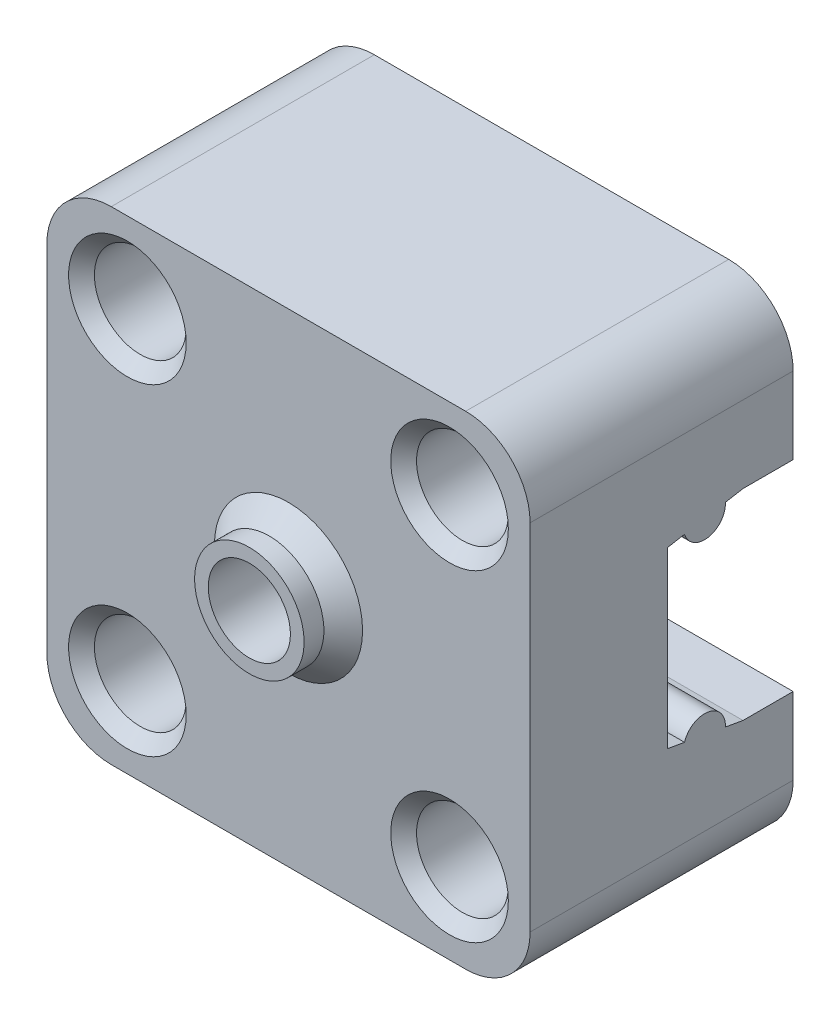
SolidWorks part; units mm, degrees
note: The reader was unsure of these and kept them because the rebuilt part matched: shared geometry of "Sketch1<3>".
ref_plane "Front Plane" through (0, 0, 0) normal (0, 0, 1) x (1, 0, 0)
ref_plane "Top Plane" through (0, 0, 0) normal (0, 1, 0) x (1, 0, 0)
ref_plane "Right Plane" through (0, 0, 0) normal (1, 0, 0) x (0, 0, -1)
sketch "Sketch1" plane through (0, 0, 0) normal (0, 0, 1) x (1, 0, 0)
  line L0 (10, 20) -> (10, 0) construction
  line L1 (0, 0) -> (20, 0) construction
  line L2 (0, 0) -> (0, 20) construction
  line L3 (0, 20) -> (20, 20) construction
  line L4 (20, 0) -> (20, 20) construction
  line L5 (10, 10) -> (68.0208, 10) construction
  line L6 (-5, -5) -> (25, -5)
  line L7 (-5, -5) -> (-5, 25)
  line L8 (-5, 25) -> (25, 25)
  line L9 (25, -5) -> (25, 25)
  line L10 (-5, -5) -> (25, 25) construction
  line L11 (-5, 25) -> (25, -5) construction
  line L13 (25, 16) -> (95, 16)
  line L14 (25, 16) -> (25, 4)
  line L15 (25, 4) -> (95, 4)
  line L16 (95, 16) -> (95, 4)
  circle A0 centre (0, 0) radius 1.6
  circle A1 centre (0, 20) radius 1.6
  circle A2 centre (20, 20) radius 1.6
  circle A3 centre (20, 0) radius 1.6
  point P11 (10, 10)
  dimension "D2" = 3.2
  dimension "D1" = 20
  dimension "D3" = 30
  dimension "D4" = 30
  dimension "D5" = 12
  dimension "D6" = 6
  dimension "D7" = 70
extrude "Boss-Extrude1" add sketch "Sketch1" along normal blind 6 contours L6 L9 L8 L7 A3 A2 A1 A0 | L16 L13 L9 L15
extrude "Boss-Extrude2" add sketch "Sketch1<3>" along normal blind 22.33 contours L6 L9 L8 L7 A3 A2 A1 A0
sketch "Sketch1<3>" plane through (0, 0, 0) normal (0, 0, 1) x (1, 0, 0) same geometry as "Sketch1"
sketch "Sketch2" plane through (25, 0, 0) normal (1, 0, 0) x (0, 0, -1)
  line L0 (-6.5155, 16.2317) -> (-9.1122, 16.2317)
  line L1 (-9.1122, 16.2317) -> (-10.2045, 16.0391)
  line L2 (-12.7425, 15.5915) -> (-13.7862, 15.4075)
  line L3 (-13.7862, 15.4075) -> (-13.7862, 4.5918)
  line L4 (-13.7862, 4.5918) -> (-12.7425, 4.4077)
  line L5 (-10.2045, 3.9602) -> (-9.1122, 3.7676)
  line L6 (-9.1122, 3.7676) -> (-6.5155, 3.7676)
  line L7 (-6.5155, 3.7676) -> (-5.9025, 3.7676)
  line L9 (-5.9025, 16.2317) -> (-6.5155, 16.2317)
  line L11 (-22.33, -5) -> (0, -5) construction
  line L12 (-22.33, -5) -> (-22.33, 25) construction
  line L13 (-5.9025, 16.2317) -> (-5.9025, 3.7676)
  arc A0 (-12.7425, 15.5915) -> (-10.2045, 16.0391) centre (-11.5011, 15.972) ccw
  arc A1 (-10.2045, 3.9602) -> (-12.7425, 4.4077) centre (-11.5011, 4.0273) ccw
extrude "Cut-Extrude1" cut sketch "Sketch2" against normal through all
sketch "Sketch3" plane through (0, 0, 22.33) normal (0, 0, 1) x (1, 0, 0)
  line L0 (-5, 10) -> (25, 10) construction
  line L1 (-5, -5) -> (-5, 25) construction
  line L2 (25, -5) -> (25, 25) construction
  line L3 (10, -5) -> (10, 25) construction
  line L4 (-5, -5) -> (25, -5) construction
  line L5 (-5, 25) -> (25, 25) construction
  circle A0 centre (10, 10) radius 2.55
  dimension "D1" = 5.1
extrude "Cut-Extrude2" cut sketch "Sketch3" against normal blind 8
sketch "Sketch5" plane through (0, 0, 13.7862) normal (0, 0, -1) x (-1, 0, 0)
  line L1 (-5.3235, 10) -> (-7.6617, 14.05)
  line L2 (-7.6617, 14.05) -> (-12.3383, 14.05)
  line L3 (-12.3383, 14.05) -> (-14.6765, 10)
  line L4 (-14.6765, 10) -> (-12.3383, 5.95)
  line L5 (-12.3383, 5.95) -> (-7.6617, 5.95)
  line L6 (-7.6617, 5.95) -> (-5.3235, 10)
  line L8 (-25, 15.4075) -> (-25, 4.5918)
  line L9 (-25, 4.5918) -> (5, 4.5918)
  line L10 (5, 4.5918) -> (5, 15.4075)
  line L11 (5, 15.4075) -> (-25, 15.4075)
  line L12 (-25, 15.4075) -> (-25, 4.5918)
  line L13 (-25, 4.5918) -> (5, 4.5918)
  line L15 (5, 15.4075) -> (-25, 15.4075)
  line L18 (5, 4.5918) -> (5, 15.4075)
  circle A0 centre (-10, 10) radius 4.05
  circle A1 centre (-10, 10) radius 4.05 construction
  dimension "D2" = 8.1
  dimension "D3" = 8.1
  dimension "D1" = 0
extrude "Cut-Extrude3" cut sketch "Sketch5" against normal blind 4.5
sketch "Sketch6" plane through (0, 0, 0) normal (0, 0, -1) x (-1, 0, 0)
  line L0 (-20, 0) -> (0, 20) construction
  line L1 (0, 20) -> (0, 0) construction
  line L2 (0, 0) -> (-20, 20) construction
  circle A0 centre (-10, 10) radius 5
  dimension "D1" = 10
extrude "Cut-Extrude5" cut sketch "Sketch6" against normal blind 8.6
sketch "Sketch7" plane through (0, 0, 0) normal (0, 0, -1) x (-1, 0, 0)
  line L1 (5, -5) -> (-3.5, -5)
  line L2 (5, -5) -> (5, 25)
  line L3 (5, 25) -> (-3.5, 25)
  line L4 (-3.5, -5) -> (-3.5, 25)
  line L5 (5, 25) -> (-25, 25) construction
  line L6 (-95, 10) -> (-3.5, 10) construction
  line L7 (-95, 16) -> (-95, 4) construction
  line L8 (-3.5, 10) -> (-3.5, 16)
  line L9 (-25, 4) -> (-95, 4) construction
  line L10 (-3.5, 16) -> (-65, 16)
  line L11 (-3.5, 16) -> (-3.5, 4)
  line L12 (-3.5, 4) -> (-65, 4)
  line L13 (-65, 16) -> (-65, 4)
  circle A0 centre (-38.5, 10) radius 1.6
  circle A1 centre (-63.5, 10) radius 1.6
  circle A2 centre (-88.5, 10) radius 1.6
  dimension "D4" = 35
  dimension "D5" = 60
  dimension "D6" = 3.2
  dimension "D7" = 3.2
  dimension "D1" = 30
  dimension "D2" = 8.5
  dimension "D3" = 6
  dimension "D8" = 25
extrude "Cut-Extrude6" cut sketch "Sketch7" against normal through all contours L6 A2 | A2 L6 | A1 | A0
sketch "Sketch8" plane through (0, 0, 22.33) normal (0, 0, 1) x (1, 0, 0)
  circle A0 centre (20, 20) radius 2.85
  circle A1 centre (20, 0) radius 2.85
  circle A2 centre (0, 0) radius 2.85
  circle A3 centre (0, 20) radius 2.85
  dimension "D4" = 5.7
extrude "Cut-Extrude7" cut sketch "Sketch8" against normal blind 11
sketch "Sketch9" plane through (0, 0, 22.33) normal (0, 0, 1) x (1, 0, 0)
  circle A0 centre (10, 10) radius 2.55
  circle A1 centre (10, 10) radius 3.4
  dimension "D1" = 5.1
  dimension "D2" = 6.8
extrude "Boss-Extrude3" add sketch "Sketch9" along normal blind 2.43
chamfer "Chamfer1" distance 1.2 angle 45 1 edges at (13.4, 10, 22.33)
fillet "Fillet3" radius 4 8 edges at (25, 4, 2.9513) (25, 16, 2.9513) (25, 25, 11.165) (-5, 25, 11.165) (-5, -5, 11.165) (25, -5, 11.165) (95, 4, 3) (95, 16, 3)
chamfer "Chamfer2" distance 0.8 angle 45 4 edges at (22.85, 0, 22.33) (2.85, 0, 22.33) (2.85, 20, 22.33) (22.85, 20, 22.33)
sketch "Sketch10" plane through (0, 0, 0) normal (0, 0, -1) x (-1, 0, 0)
  line L1 (-85.2668, 10) -> (-86.8834, 12.8)
  line L2 (-86.8834, 12.8) -> (-90.1166, 12.8)
  line L3 (-90.1166, 12.8) -> (-91.7332, 10)
  line L4 (-91.7332, 10) -> (-90.1166, 7.2)
  line L5 (-90.1166, 7.2) -> (-86.8834, 7.2)
  line L6 (-86.8834, 7.2) -> (-85.2668, 10)
  circle A3 centre (-88.5, 10) radius 2.8 construction
  dimension "D1" = 5.6
extrude "Cut-Extrude8" cut sketch "Sketch10" against normal blind 3
chamfer "Chamfer3" distance 0.8 angle 45 6 edges at (86.0751, 8.6, 0) (88.5, 7.2, 0) (90.9249, 8.6, 0) (90.9249, 11.4, 0) (86.0751, 11.4, 0) (88.5, 12.8, 0)
pattern_linear "LPattern1" count 3 spacing 25 along (-1, 0, 0) of "Chamfer3", "Cut-Extrude8"
sketch "Sketch12" plane through (0, 0, 0) normal (0, 0, -1) x (-1, 0, 0)
  line L1 (6.555, -7.0675) -> (-96.6557, -7.0675)
  line L2 (6.555, -7.0675) -> (6.555, 26.7654)
  line L3 (6.555, 26.7654) -> (-96.6557, 26.7654)
  line L4 (-96.6557, -7.0675) -> (-96.6557, 26.7654)
extrude "Cut-Extrude9" cut sketch "Sketch12" against normal blind 6
